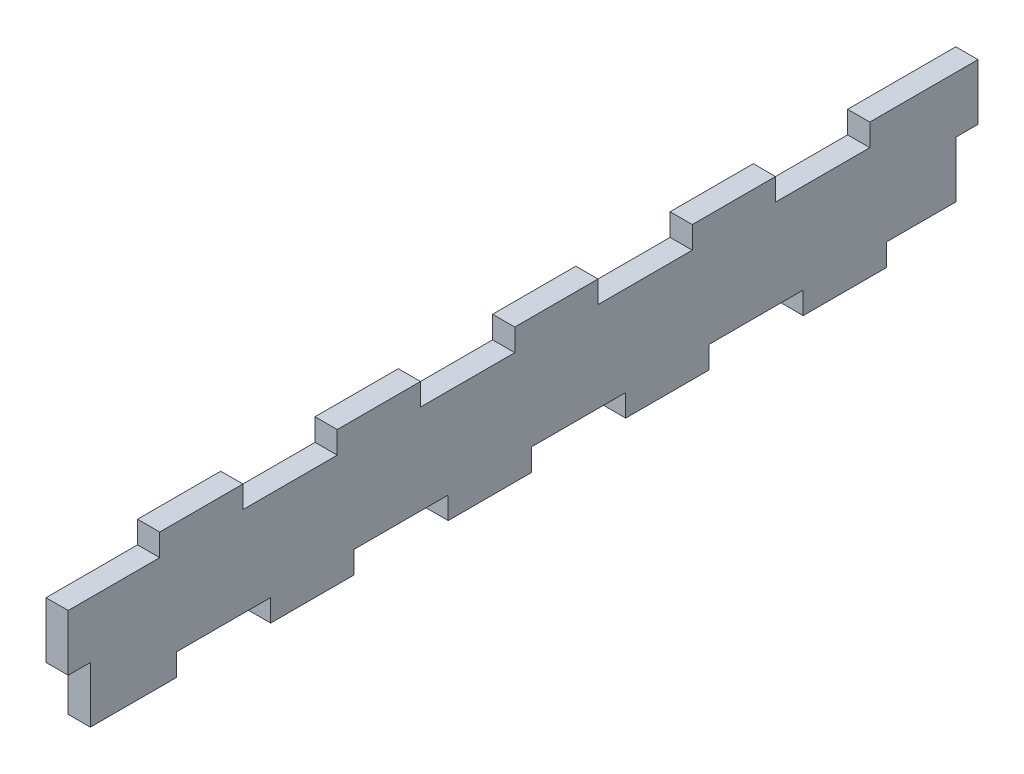
SolidWorks part; units mm, degrees
ref_plane "Plan de face" through (0, 0, 0) normal (0, 0, 1) x (1, 0, 0)
ref_plane "Plan de dessus" through (0, 0, 0) normal (0, 1, 0) x (1, 0, 0)
ref_plane "Plan de droite" through (0, 0, 0) normal (1, 0, 0) x (0, 0, -1)
sketch "Esquisse1" plane through (0, 0, 0) normal (1, 0, 0) x (0, 0, -1)
  line L5 (-41.0892, -6.055) -> (40.9108, -6.055)
  line L6 (-41.0892, -6.055) -> (-41.0892, 6.055)
  line L7 (-41.0892, 6.055) -> (40.9108, 6.055)
  line L8 (40.9108, -6.055) -> (40.9108, 6.055)
  point P4 (0, 0)
  point P5 (0, 0)
  point P6 (0, 0)
extrude "Boss.-Extru.1" add sketch "Esquisse1" along normal blind 2
sketch "Esquisse2" plane through (0, 0, 0) normal (1, 0, 0) x (0, 0, -1)
  line L0 (-33.0892, 4.055) -> (-33.0892, 6.055) construction
  line L1 (-41.3392, 6.305) -> (-32.8392, 6.305)
  line L2 (-41.3392, 6.305) -> (-41.3392, 4.055)
  line L3 (-41.3392, 4.055) -> (-32.8392, 4.055)
  line L4 (-32.8392, 6.305) -> (-32.8392, 4.055)
  line L5 (-41.0892, 6.305) -> (-41.0892, 6.055) construction
  line L6 (-41.0892, 6.055) -> (-41.3392, 6.055) construction
  line L8 (-33.0892, 5.18) -> (-32.8392, 5.18) construction
  line L9 (-41.0892, 4.055) -> (-33.0892, 4.055) construction
  line L11 (-25.3392, 6.305) -> (-16.8392, 6.305)
  line L12 (-16.8392, 6.305) -> (-16.8392, 4.055)
  line L13 (-25.3392, 4.055) -> (-16.8392, 4.055)
  line L14 (-25.3392, 6.305) -> (-25.3392, 4.055)
  line L15 (-9.3392, 6.305) -> (-0.8392, 6.305)
  line L16 (-0.8392, 6.305) -> (-0.8392, 4.055)
  line L17 (-9.3392, 4.055) -> (-0.8392, 4.055)
  line L18 (-9.3392, 6.305) -> (-9.3392, 4.055)
  line L19 (6.6608, 6.305) -> (15.1608, 6.305)
  line L20 (15.1608, 6.305) -> (15.1608, 4.055)
  line L21 (6.6608, 4.055) -> (15.1608, 4.055)
  line L22 (6.6608, 6.305) -> (6.6608, 4.055)
  line L23 (22.6608, 6.305) -> (31.1608, 6.305)
  line L24 (31.1608, 6.305) -> (31.1608, 4.055)
  line L25 (22.6608, 4.055) -> (31.1608, 4.055)
  line L26 (22.6608, 6.305) -> (22.6608, 4.055)
  line L27 (-32.8392, 4.055) -> (-25.3392, 4.055) construction
  line L29 (-25.3392, 5.18) -> (-25.0892, 5.18) construction
  line L30 (-25.0892, 6.055) -> (-25.0892, 4.055) construction
  dimension "D3" = 0.25
  dimension "D2" = 5
extrude "Enlèv. mat.-Extru.1" cut sketch "Esquisse2" along normal through all
sketch "Esquisse3" plane through (0, 0, 0) normal (1, 0, 0) x (0, 0, -1)
  line L0 (-41.0892, -6.055) -> (40.9108, -6.055) construction
  line L1 (-31.3392, -6.055) -> (-22.8392, -6.055)
  line L2 (-31.3392, -6.055) -> (-31.3392, -4.055)
  line L3 (-31.3392, -4.055) -> (-22.8392, -4.055)
  line L4 (-22.8392, -6.055) -> (-22.8392, -4.055)
  line L7 (-25.3392, 4.055) -> (-16.8392, 4.055) construction
  line L8 (-32.8392, 4.055) -> (-32.8392, 6.055) construction
  line L9 (-31.3392, -5.055) -> (-31.0892, -5.055) construction
  line L10 (-31.0892, -6.055) -> (-31.0892, -4.055) construction
  line L11 (-32.8392, 5.2908) -> (-33.0892, 5.2908) construction
  line L12 (-32.8392, 4.055) -> (-32.8392, 6.055) construction
  line L13 (-33.0892, 4.055) -> (-33.0892, 6.055) construction
  line L14 (-15.3392, -6.055) -> (-6.8392, -6.055)
  line L15 (-15.3392, -6.055) -> (-15.3392, -4.055)
  line L16 (-15.3392, -4.055) -> (-6.8392, -4.055)
  line L17 (-6.8392, -6.055) -> (-6.8392, -4.055)
  line L18 (-15.3392, -5.055) -> (-15.0892, -5.055) construction
  line L19 (0.6608, -6.055) -> (9.1608, -6.055)
  line L20 (0.6608, -6.055) -> (0.6608, -4.055)
  line L21 (0.6608, -4.055) -> (9.1608, -4.055)
  line L22 (9.1608, -6.055) -> (9.1608, -4.055)
  line L23 (0.6608, -5.055) -> (0.9108, -5.055) construction
  line L24 (16.6608, -6.055) -> (25.1608, -6.055)
  line L25 (16.6608, -6.055) -> (16.6608, -4.055)
  line L26 (16.6608, -4.055) -> (25.1608, -4.055)
  line L27 (25.1608, -6.055) -> (25.1608, -4.055)
  line L28 (16.6608, -5.055) -> (16.9108, -5.055) construction
  line L29 (32.6608, -6.055) -> (41.1608, -6.055)
  line L30 (32.6608, -6.055) -> (32.6608, -4.055)
  line L31 (32.6608, -4.055) -> (41.1608, -4.055)
  line L32 (41.1608, -6.055) -> (41.1608, -4.055)
  line L33 (32.6608, -5.055) -> (32.9108, -5.055) construction
  line L40 (48.6608, -6.055) -> (57.1608, -6.055) [skipped]
  line L41 (48.6608, -6.055) -> (48.6608, -4.055) [skipped]
  line L42 (48.6608, -4.055) -> (57.1608, -4.055) [skipped]
  line L43 (48.6608, -5.055) -> (48.9108, -5.055) construction
  line L44 (57.1608, -6.055) -> (57.1608, -4.055) [skipped]
  line L45 (40.9108, -6.055) -> (40.9108, -4.055) construction
  dimension "D2" = 0.25
  dimension "D1" = 6
extrude "Enlèv. mat.-Extru.2" cut sketch "Esquisse3" along normal through all
sketch "Esquisse4" plane through (2, 0, 0) normal (1, 0, 0) x (0, 0, -1)
  line L0 (-39.0892, -1) -> (-39.0892, 4.055) construction
  line L1 (-41.0892, -6.055) -> (-39.0892, -6.055)
  line L2 (-41.0892, -6.055) -> (-41.0892, -1)
  line L3 (-41.0892, -1) -> (-39.0892, -1)
  line L4 (-39.0892, -6.055) -> (-39.0892, -1)
  line L5 (-41.0892, 4.055) -> (-33.0892, 4.055) construction
  line L6 (-41.0892, 6.055) -> (-41.0892, 4.055) construction
  line L8 (40.9108, -4.055) -> (38.9108, -4.055)
  line L9 (40.9108, -4.055) -> (40.9108, 1)
  line L10 (40.9108, 1) -> (38.9108, 1)
  line L11 (38.9108, -4.055) -> (38.9108, 1)
extrude "Enlèv. mat.-Extru.3" cut sketch "Esquisse4" against normal through all
